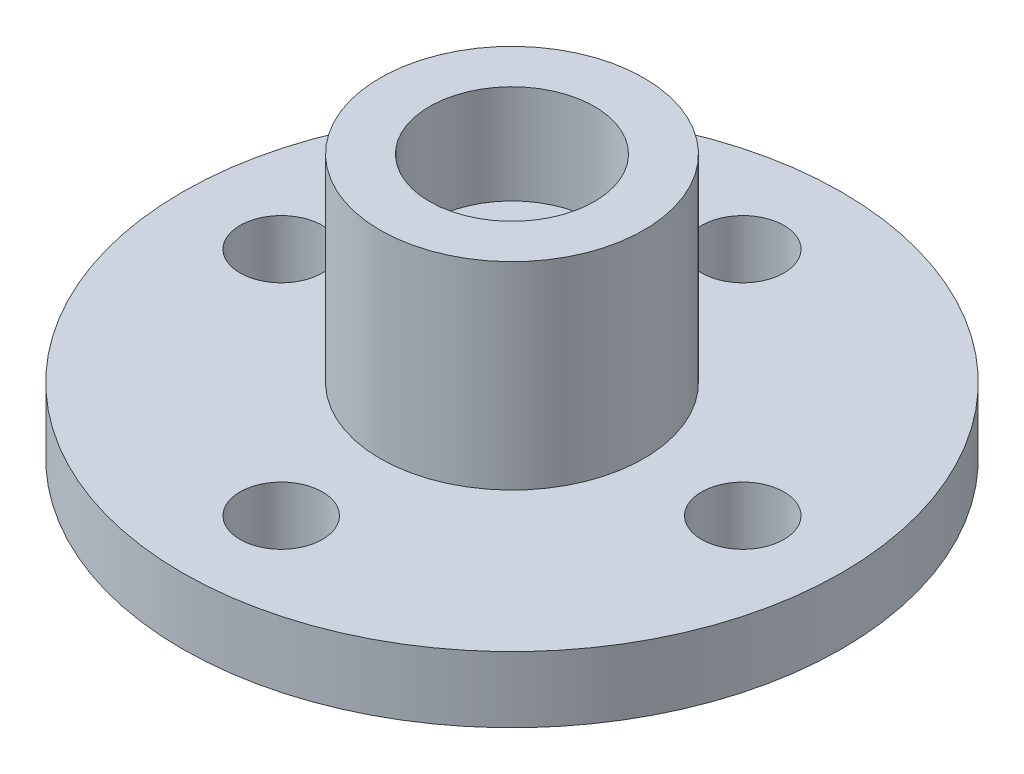
SolidWorks part; units mm, degrees
material "6061 Alloy"
ref_plane "Front Plane" through (0, 0, 0) normal (0, 0, 1) x (1, 0, 0)
ref_plane "Top Plane" through (0, 0, 0) normal (0, 1, 0) x (1, 0, 0)
ref_plane "Right Plane" through (0, 0, 0) normal (1, 0, 0) x (0, 0, -1)
sketch "Sketch1" plane through (0, 0, 0) normal (0, 1, 0) x (1, 0, 0)
  circle A0 centre (0, 0) radius 10
  dimension "D1" = 20
extrude "Boss-Extrude1" add sketch "Sketch1" along normal blind 2
ref_axis "Axis1" through (0, 2, 0) along (0, -1, 0)
hole_wizard "Tap Drill for M3x0.5 Tap1" positions "Sketch2" profile "Sketch3" hole size "M3x0.5" standard "ANSI Metric"
sketch "Sketch2" plane through (0, 2, 0) normal (0, 1, 0) x (1, 0, 0)
  point P0 (7, 0)
  dimension "D1" = 7
sketch "Sketch3" plane through (7, 2, 0) normal (1, 0, 0) x (0, 0, 1)
  line L0 (0, 0) -> (0, 38.1)
  line L1 (0, 38.1) -> (1.25, 38.1)
  line L2 (1.25, 38.1) -> (1.25, 0)
  line L5 (1.25, 0) -> (0, 0)
  line L10 (0, 38.1) -> (-1.25, 38.1) construction
  line L11 (0, -6.35) -> (0, 107.95) construction
  dimension "Hole Dia." = 2.5
  dimension "Hole Depth" = 38.1
  dimension "Drill Angle" = 180
pattern_circular "CirPattern1" count 4 over 360 about axis through (0, 2, 0) along (0, -1, 0) of "Tap Drill for M3x0.5 Tap1"
sketch "Sketch4" plane through (0, 2, 0) normal (0, 1, 0) x (1, 0, 0)
  circle A0 centre (0, 0) radius 4
  dimension "D1" = 8
extrude "Boss-Extrude2" add sketch "Sketch4" along normal blind 6
sketch "Sketch5" plane through (0, 8, 0) normal (0, 1, 0) x (1, 0, 0)
  circle A0 centre (0, 0) radius 2.5
  dimension "D1" = 5
extrude "Cut-Extrude1" cut sketch "Sketch5" against normal blind 3
hole_wizard "Tap Drill for M3x0.5 Tap2" positions "Sketch6" profile "Sketch7" hole size "M3x0.5" standard "ANSI Metric"
sketch "Sketch6" plane through (0, 5, 0) normal (0, 1, 0) x (1, 0, 0)
  point P0 (0, 0)
sketch "Sketch7" plane through (0, 5, 0) normal (1, 0, 0) x (0, 0, 1)
  line L0 (0, 0) -> (0, 38.1)
  line L1 (0, 38.1) -> (1.25, 38.1)
  line L2 (1.25, 38.1) -> (1.25, 0)
  line L5 (1.25, 0) -> (0, 0)
  line L10 (0, 38.1) -> (-1.25, 38.1) construction
  line L11 (0, -6.35) -> (0, 107.95) construction
  dimension "Hole Dia." = 2.5
  dimension "Hole Depth" = 38.1
  dimension "Drill Angle" = 180
